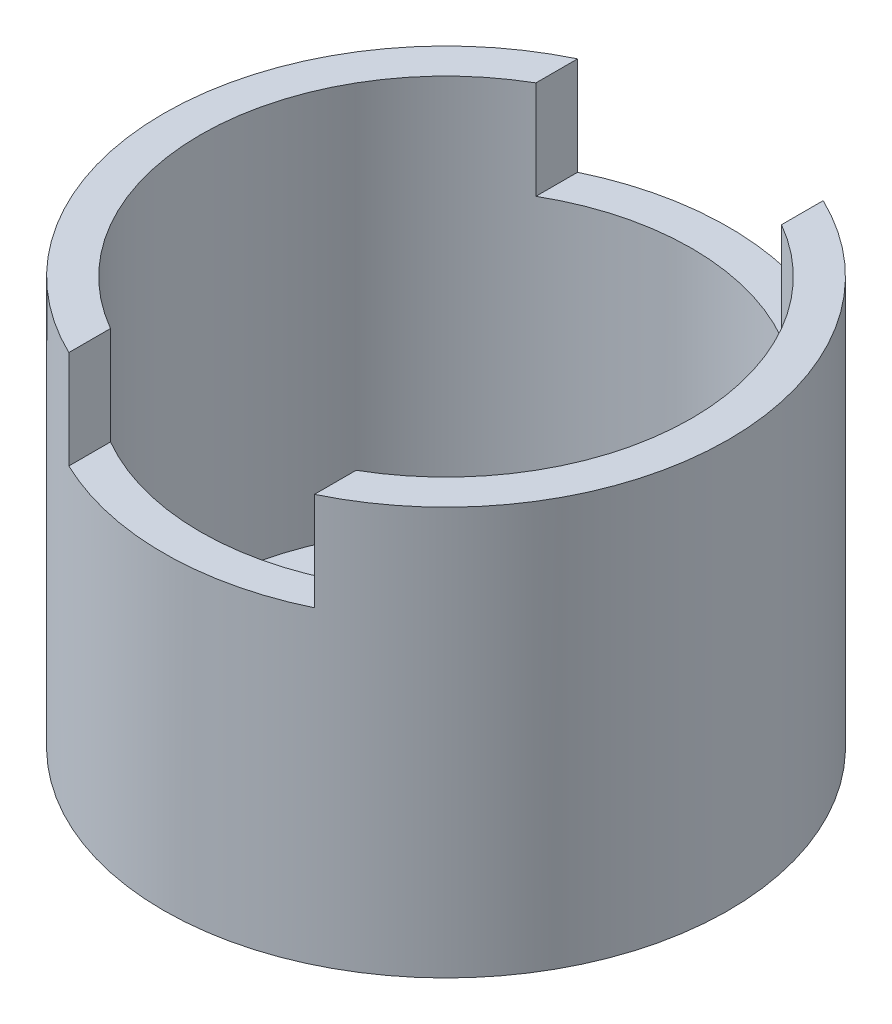
SolidWorks part; units mm, degrees
ref_plane "前视基准面" through (0, 0, 0) normal (0, 0, 1) x (1, 0, 0)
ref_plane "上视基准面" through (0, 0, 0) normal (0, 1, 0) x (1, 0, 0)
ref_plane "右视基准面" through (0, 0, 0) normal (1, 0, 0) x (0, 0, -1)
sketch "草图1" plane through (0, 0, 0) normal (0, 1, 0) x (1, 0, 0)
  line L1 (-11.5, 11.5) -> (11.5, 11.5) construction
  line L2 (-11.5, 11.5) -> (-11.5, -11.5) construction
  line L3 (-11.5, -11.5) -> (11.5, -11.5) construction
  line L4 (11.5, 11.5) -> (11.5, -11.5) construction
  line L5 (-11.5, 11.5) -> (11.5, -11.5) construction
  line L6 (-11.5, -11.5) -> (11.5, 11.5) construction
  circle A0 centre (0, 0) radius 75
  circle A1 centre (11.5, 11.5) radius 1.4
  circle A2 centre (-11.5, 11.5) radius 1.4
  circle A3 centre (-11.5, -11.5) radius 1.4
  circle A4 centre (11.5, -11.5) radius 1.4
  circle A5 centre (0, 0) radius 50 construction
  circle A6 centre (0, 50) radius 17.5
  circle A7 centre (50, 0) radius 17.5
  circle A8 centre (0, -50) radius 17.5
  circle A9 centre (-50, 0) radius 17.5
  circle A10 centre (0, 0) radius 13.5
  point P23 (0, 0)
  dimension "D3" = 2.8
  dimension "D4" = 2.8
  dimension "D5" = 2.8
  dimension "D6" = 2.8
  dimension "D7" = 150
  dimension "D8" = 100
  dimension "D9" = 35
  dimension "D11" = 27
  dimension "D1" = 23
  dimension "D2" = 23
  dimension "D10" = 4
extrude "凸台-拉伸1" add sketch "草图1" along normal blind 3 contours A0 | A3 | A4 | A2 | A1 | A10
ref_plane "基准面1" through (0, 3, 0) normal (0, 1, 0) x (1, 0, 0)
sketch "草图2" plane through (0, 3, 0) normal (0, 1, 0) x (1, 0, 0)
  circle A0 centre (0, 0) radius 50
  circle A1 centre (0, 0) radius 57.5
  dimension "D1" = 100
  dimension "D2" = 115
extrude "凸台-拉伸3" add sketch "草图2" along normal blind 80
sketch "草图4" plane through (0, 0, 0) normal (0, 0, 1) x (1, 0, 0)
  line L0 (57.5, 83) -> (-57.5, 83) construction
  line L1 (-25, 103) -> (25, 103)
  line L2 (-25, 103) -> (-25, 63)
  line L3 (-25, 63) -> (25, 63)
  line L4 (25, 103) -> (25, 63)
  line L5 (-25, 103) -> (25, 63) construction
  line L6 (-25, 63) -> (25, 103) construction
  point P0 (0, 83)
  dimension "D1" = 40
  dimension "D2" = 50
extrude "切除-拉伸1" cut sketch "草图4" against normal blind 80 and the other way blind 80
sketch "草图5" plane through (0, 3, 0) normal (0, 1, 0) x (1, 0, 0)
  circle A0 centre (0, 0) radius 57.5
  circle A1 centre (0, 0) radius 75
extrude "切除-拉伸2" cut sketch "草图5" against normal blind 80
